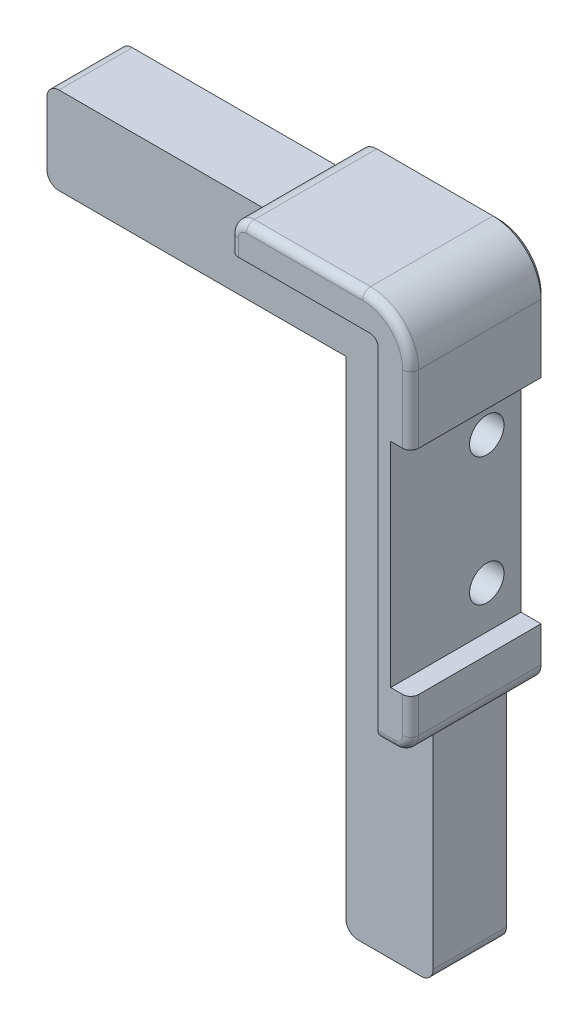
SolidWorks part; units mm, degrees
ref_plane "Front Plane" through (0, 0, 0) normal (0, 0, 1) x (1, 0, 0)
ref_plane "Top Plane" through (0, 0, 0) normal (0, 1, 0) x (1, 0, 0)
ref_plane "Right Plane" through (0, 0, 0) normal (1, 0, 0) x (0, 0, -1)
ref_plane "PZ 20.375" through (0, 0, 20.375) normal (0, 0, 1) x (1, 0, 0)
sketch "body and tongues sketch" plane through (0, 0, 20.375) normal (0, 0, 1) x (1, 0, 0)
  line L0 (4.42, 7.07) -> (-18.08, 7.07)
  line L1 (-18.08, 7.07) -> (-18.08, 2.75)
  line L2 (-18.08, 2.75) -> (-48.08, 2.75)
  line L3 (-48.08, 2.75) -> (-48.08, -8.13)
  line L4 (-48.08, -8.13) -> (-10.78, -8.13)
  line L5 (-10.78, -8.13) -> (-10.78, -70.43)
  line L6 (-10.78, -70.43) -> (0.1, -70.43)
  line L7 (0.1, -70.43) -> (0.1, -40.43)
  line L8 (0.1, -40.43) -> (4.42, -40.43)
  line L9 (4.42, -40.43) -> (4.42, 7.07)
extrude "body and tongues" add sketch "body and tongues sketch" along normal mid plane 9.75
ref_plane "PZ 23.935" through (0, 0, 23.935) normal (0, 0, 1) x (1, 0, 0)
sketch "rim sketch" plane through (0, 0, 23.935) normal (0, 0, 1) x (1, 0, 0)
  line L0 (4.42, 7.07) -> (-18.08, 7.07)
  line L1 (-18.08, 7.07) -> (-18.08, 3)
  line L2 (-18.08, 3) -> (0.35, 3)
  line L3 (0.35, 3) -> (0.35, -40.43)
  line L4 (0.35, -40.43) -> (4.42, -40.43)
  line L5 (4.42, -40.43) -> (4.42, 7.07)
extrude "rim" add sketch "rim sketch" along normal mid plane 16.87
sketch "bracket seat sketch" plane through (0, 0, 23.935) normal (0, 0, 1) x (1, 0, 0)
  line L0 (1.92, -34) -> (5.42, -34)
  line L1 (5.42, -34) -> (5.42, -7.4)
  line L2 (5.42, -7.4) -> (1.92, -7.4)
  line L3 (1.92, -7.4) -> (1.92, -34)
extrude "bracket seat" cut sketch "bracket seat sketch" against normal mid plane 18.87
ref_plane "PX -1.580" through (-1.58, 0, 0) normal (1, 0, 0) x (0, 0, -1)
sketch "screw pilots sketch" plane through (-1.58, 0, 0) normal (1, 0, 0) x (0, 0, -1)
  circle A0 centre (-20.375, -28.7) radius 2.15
  circle A1 centre (-20.375, -12.7) radius 2.15
extrude "screw pilots" cut sketch "screw pilots sketch" against normal mid plane 9
fillet "bumper corner" radius 6 1 edges at (4.42, 7.07, 23.935) tangent propagation no
fillet "inside corner of the rim" radius 1 1 edges at (0.35, 3, 28.81) tangent propagation no
fillet "rim ends" radius 2 2 edges at (-18.08, 7.07, 23.935) (4.42, -40.43, 23.935) tangent propagation no
fillet "tongue lead-in" radius 1.5 4 edges at (-48.08, -8.13, 20.375) (-48.08, 2.75, 20.375) (-10.78, -70.43, 20.375) (0.1, -70.43, 20.375) tangent propagation no
fillet "rim top edge" radius 1 7 edges at (4.42, -36.215, 32.37) (2.6626, 5.3126, 32.37) (-18.08, 4.035, 32.37) (-17.4942, 6.4842, 32.37) (1.385, -40.43, 32.37) (3.8342, -39.8442, 32.37) (-8.83, 7.07, 32.37)
chamfer "bed face chamfer" distance 0.6 angle 45 20 edges at (-10.78, -38.53, 15.5) (-10.3407, -69.9907, 15.5) (-5.34, -70.43, 15.5) (-0.3393, -69.9907, 15.5) (0.1, -54.68, 15.5) (1.26, -40.43, 15.5) (3.8342, -39.8442, 15.5) (4.42, -3.165, 15.5) (3.17, -34, 15.5) (1.92, -20.7, 15.5) (3.17, -7.4, 15.5) (2.6626, 5.3126, 15.5) (-8.83, 7.07, 15.5) (-17.4942, 6.4842, 15.5) (-18.08, 3.91, 15.5) (-32.33, 2.75, 15.5) (-47.6407, 2.3107, 15.5) (-48.08, -2.69, 15.5) (-47.6407, -7.6907, 15.5) (-28.68, -8.13, 15.5)
equation "\"diffL\" = 608.8mm"
equation "\"diffW\" = 329.4mm"
equation "\"diffT\" = 2.9mm"
equation "\"chanSlotW\" = 12.9mm"
equation "\"chanSlotDepth\" = 11.13mm"
equation "\"chanFloor\" = 1.57mm"
equation "\"chanLeg\" = 12.7mm"
equation "\"lightL\" = 605mm"
equation "\"lightW\" = 331mm"
equation "\"lightH\" = 92mm"
equation "\"lightSideFlat\" = 30mm"
equation "\"lightSlopeLen\" = 33.1mm"
equation "\"lightWingDepth\" = 47.9mm"
equation "\"lightWingFlat\" = 90.2mm"
equation "\"lightChanW\" = 99.6mm"
equation "\"lightChanStand\" = 44.1mm"
equation "\"insFlangeD\" = 12.3mm"
equation "\"insFromEnd\" = 20.7mm"
equation "\"insUpSlope\" = 20.8mm"
equation "\"gaugeH\" = 10mm"
equation "\"gaugeStepLen\" = 14mm"
equation "\"gaugeStepW0\" = 13.1mm"
equation "\"gaugeStepDW\" = 0.2mm"
equation "\"gaugeSteps\" = 5mm"
equation "\"gaugeHandleLen\" = 30mm"
equation "\"gaugeHandleW\" = 24mm"
equation "\"gaugeSlot0\" = 3mm"
equation "\"gaugeSlotD\" = 0.1mm"
equation "\"gaugeSlotDepth\" = 8mm"
equation "\"gap\" = 25.4mm"
equation "\"edgeL\" = 1mm"
equation "\"edgeW\" = 0.75mm"
equation "\"proud\" = 1.5mm"
equation "\"seatClr\" = 0.15mm"
equation "\"tongueClrZ\" = 0.1mm"
equation "\"tongueClrX\" = 0.25mm"
equation "\"tongueLen\" = 30mm"
equation "\"armSide\" = 45mm"
equation "\"armEnd\" = 20mm"
equation "\"cornerCham\" = 3mm"
equation "\"brkW\" = 26mm"
equation "\"brkT\" = 7mm"
equation "\"brkSeatClr\" = 0.2mm"
equation "\"brkScrewSpan\" = 16mm"
equation "\"pilotD\" = 2.7mm"
equation "\"pilotDepth\" = 10mm"
equation "\"screwClrD\" = 3.9mm"
equation "\"jogBelow\" = 4mm"
equation "\"padT\" = 7mm"
equation "\"padLen\" = 31mm"
equation "\"m6Clr\" = 7mm"
equation "\"m6Slot\" = 3mm"
equation "\"flangeRelD\" = 17mm"
equation "\"flangeRelDepth\" = 1.5mm"
equation "\"relLen\" = 7mm"
equation "\"relDepth\" = 4mm"
equation "\"relLand\" = 2mm"
equation "\"knockN\" = 100mm"
equation "\"petgcfE\" = 3000mm"
equation "\"mockExtent\" = 110mm"
equation "\"relZnear\" = 9.4mm"
equation "\"relZfar\" = 23.4mm"
equation "\"headD\" = 8mm"
equation "\"headH\" = 2.5mm"
equation "\"headFromEnd\" = 6.8mm"
equation "\"headBack\" = 16.4mm"
equation "\"sideClr\" = 0.4mm"
equation "\"cornerRelR\" = 1.5mm"
equation "\"cornerRelBack\" = 0.6mm"
equation "\"endHeadH\" = 2.8mm"
equation "\"footClr\" = 1.2mm"
equation "\"footEndClr\" = 3.5mm"
equation "\"footLift\" = 6mm"
equation "\"footBlockClr\" = 0.5mm"
equation "\"footBack\" = 50mm"
equation "\"footFwd\" = 10mm"
equation "\"footBraceEnd\" = 3mm"
equation "\"footLoadN\" = 25mm"
equation "\"spacerLen\" = 60mm"
equation "\"spacerShort\" = 0.5mm"
equation "\"spacerCham\" = 0.8mm"
equation "\"spacerPerSide\" = 3mm"
equation "\"spacerPerEnd\" = 1mm"
equation "\"toolR\" = 9mm"
equation "\"visR\" = 4mm"
equation "\"edgeR\" = 1mm"
equation "\"bendOutR\" = 5mm"
equation "\"insideR\" = 2.5mm"
equation "\"footCornerR\" = 10mm"
equation "\"footFrontR\" = 8mm"
equation "\"braceKinkR\" = 12mm"
equation "\"bedCham\" = 1mm"
equation "\"bedChamSmall\" = 0.6mm"
equation "\"soleTopR\" = 2mm"
equation "\"cornerR\" = 6mm"
equation "\"rimInR\" = 1mm"
equation "\"insFlangeH\" = 1mm"
equation "\"insHoleFinishD\" = 4.5mm"
equation "\"insLen\" = 6.4mm"
